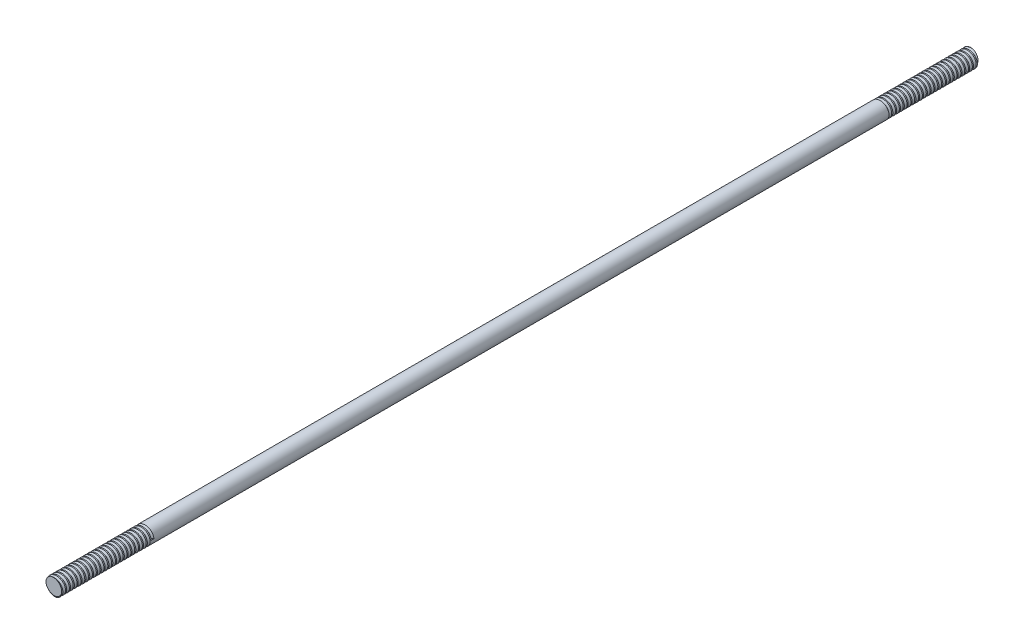
SolidWorks part; units mm, degrees
material "6061 Alloy"
ref_plane "Front Plane" through (0, 0, 0) normal (0, 0, 1) x (1, 0, 0)
ref_plane "Top Plane" through (0, 0, 0) normal (0, 1, 0) x (1, 0, 0)
ref_plane "Right Plane" through (0, 0, 0) normal (1, 0, 0) x (0, 0, -1)
sketch "Sketch1" plane through (0, 0, 0) normal (0, 0, 1) x (1, 0, 0)
  circle A0 centre (0, 0) radius 1.7526
  dimension "D1" = 3.5052
extrude "Rod" add sketch "Sketch1" along normal blind 189.5935
sketch "Sketch2" plane through (0, 0, 0) normal (0, 0, -1) x (-1, 0, 0)
  circle A0 centre (0, 0) radius 1.7526 construction
  circle A1 centre (0, 0) radius 1.7526
curve "Helix/Spiral1" pitch 0.7937 height 19.05 radius 1.7526 centre (0, 0, 0) axis (0, 0, 1) start towards (-1, 0, 0)
sketch "Sketch4" plane through (0, 0, 0) normal (0, 1, 0) x (1, 0, 0)
  line L0 (-1.7526, 0) -> (1.7526, 0) construction
  line L1 (-1.7526, 0) -> (-1.7526, 0.5556)
  line L2 (-1.7526, 0.5556) -> (-1.3402, 0.3175)
  line L3 (-1.3402, 0.3175) -> (-1.3402, 0.2381)
  line L4 (-1.3402, 0.2381) -> (-1.7526, 0)
  line L5 (-1.3402, 0.2778) -> (-1.7526, 0.2778) construction
  line L6 (-1.5464, 0.4366) -> (-1.5464, 0.1191) construction
  dimension "D1" = 0.3175
  dimension "D2" = 0.0794
  dimension "D3" = 60
sweep "Thread 1" cut profiles "Sketch4" path "Helix/Spiral1"
sketch "Sketch6" plane through (0, 0, 0) normal (0, 1, 0) x (1, 0, 0)
  line L0 (1.7526, -189.5935) -> (1.7526, -190.1491)
  line L1 (1.7526, -190.1491) -> (1.3402, -189.911)
  line L2 (1.3402, -189.911) -> (1.3402, -189.8316)
  line L3 (1.3402, -189.8316) -> (1.7526, -189.5935)
  line L4 (1.3402, -189.8713) -> (1.7526, -189.8713) construction
  line L5 (1.5464, -190.03) -> (1.5464, -189.7125) construction
  line L7 (-1.7526, -189.5935) -> (1.7526, -189.5935) construction
  line L9 (-1.7526, -189.5935) -> (1.7526, -189.5935) construction
  dimension "D1" = 0.0794
  dimension "D2" = 0.3175
  dimension "D3" = 60
sketch "Sketch5" plane through (0, 0, 189.5935) normal (0, 0, 1) x (1, 0, 0)
  circle A1 centre (0, 0) radius 1.7526
  circle A2 centre (0, 0) radius 1.7526
  dimension "D1" = 0
curve "Helix/Spiral2" pitch 0.7937 height 19.05 turns 24
sweep "Thread 2" cut profiles "Sketch6" path "Helix/Spiral2"
